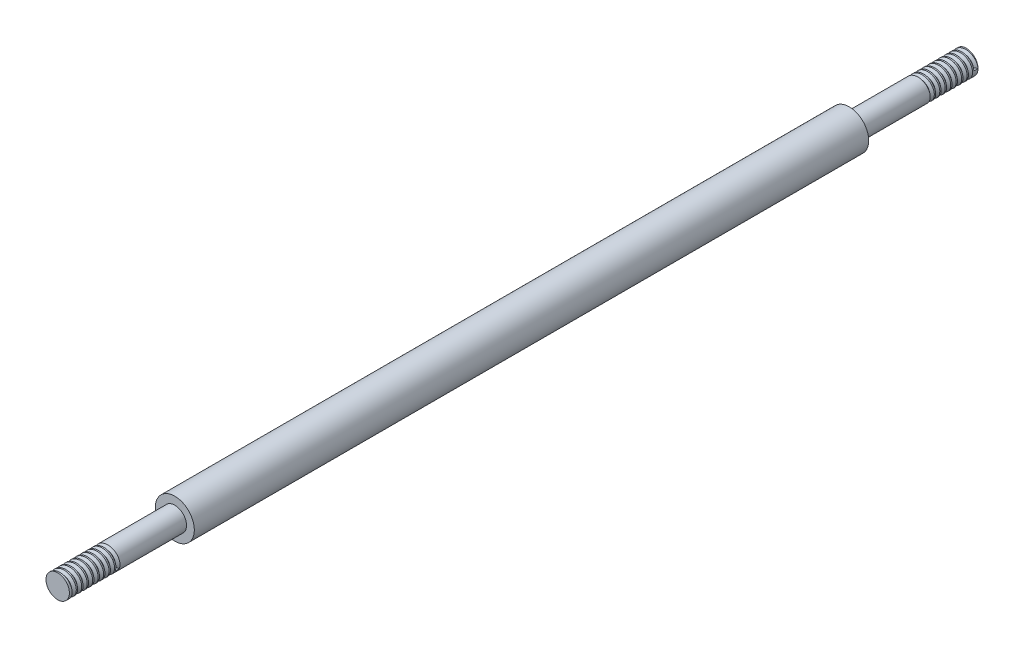
SolidWorks part; units mm, degrees
material "2014 Alloy"
ref_plane "Front Plane" through (0, 0, 0) normal (0, 0, 1) x (1, 0, 0)
ref_plane "Top Plane" through (0, 0, 0) normal (0, 1, 0) x (1, 0, 0)
ref_plane "Right Plane" through (0, 0, 0) normal (1, 0, 0) x (0, 0, -1)
sketch "Sketch1" plane through (0, 0, 0) normal (0, 0, 1) x (1, 0, 0)
  circle A0 centre (0, 0) radius 1.25
  dimension "D1" = 2.5
extrude "Boss-Extrude1" add sketch "Sketch1" along normal blind 43.2
sketch "Sketch2" plane through (0, 0, 43.2) normal (0, 0, 1) x (1, 0, 0)
  circle A0 centre (0, 0) radius 0.75
  dimension "D1" = 1.5
extrude "Boss-Extrude2" add sketch "Sketch2" along normal blind 7.5
thread "Thread1" pitch 0.35 method cut profile "Thread Profile1" start angle 0, offset 0, length 3, pitch 0.35, diameter 1.5
ref_plane "Plane1" through (-0.75, 0, 50.7) normal (0, -1, 0) x (-1, 0, 0)
sketch "Thread Profile1" plane through (-0.75, 0, 50.7) normal (0, -1, 0) x (-1, 0, 0)
  line L0 (0, 0) -> (0, 0.35) construction
  line L1 (0, 0.2625) -> (-0.1894, 0.1531)
  line L2 (-0.1894, 0.1531) -> (-0.1894, 0.1094)
  line L3 (-0.1894, 0.1094) -> (0, 0)
  line L4 (-0.1894, 0.1313) -> (0, 0.1313) construction
  line L11 (0, 0.2625) -> (0, 0)
  point P6 (0, 0)
  dimension "Pitch" = 0.35
  dimension "Profile_Angle" = 60
  dimension "Profile_Land" = 0.0437
  dimension "Profile_Height" = 0.1894
ref_plane "Plane2" through (0, 0, 21.6) normal (0, 0, -1) x (-1, 0, 0)
sketch "Sketch6" plane through (0, 0, 0) normal (0, 0, -1) x (-1, 0, 0)
  circle A0 centre (0, 0) radius 0.75
  dimension "D1" = 1.5
extrude "Boss-Extrude3" add sketch "Sketch6" along normal blind 7.5
thread "Thread2" pitch 0.35 method cut profile "Thread Profile2" start angle 0, offset 0, length 3, pitch 0.35, diameter 1.5
ref_plane "Plane3" through (0.75, 0, -7.5) normal (0, -1, 0) x (1, 0, 0)
sketch "Thread Profile2" plane through (0.75, 0, -7.5) normal (0, -1, 0) x (1, 0, 0)
  line L0 (0, 0) -> (0, 0.35) construction
  line L1 (0, 0.2625) -> (-0.1894, 0.1531)
  line L2 (-0.1894, 0.1531) -> (-0.1894, 0.1094)
  line L3 (-0.1894, 0.1094) -> (0, 0)
  line L4 (-0.1894, 0.1313) -> (0, 0.1313) construction
  line L11 (0, 0.2625) -> (0, 0)
  point P6 (0, 0)
  dimension "Pitch" = 0.35
  dimension "Profile_Angle" = 60
  dimension "Profile_Land" = 0.0437
  dimension "Profile_Height" = 0.1894
scale "Scale1" scale about centroid uniform scaling yes scale factor 0.95
scale "Scale2" scale about centroid uniform scaling yes scale factor 1.052632
scale "Scale3" scale about centroid uniform scaling yes scale factor 0.94
